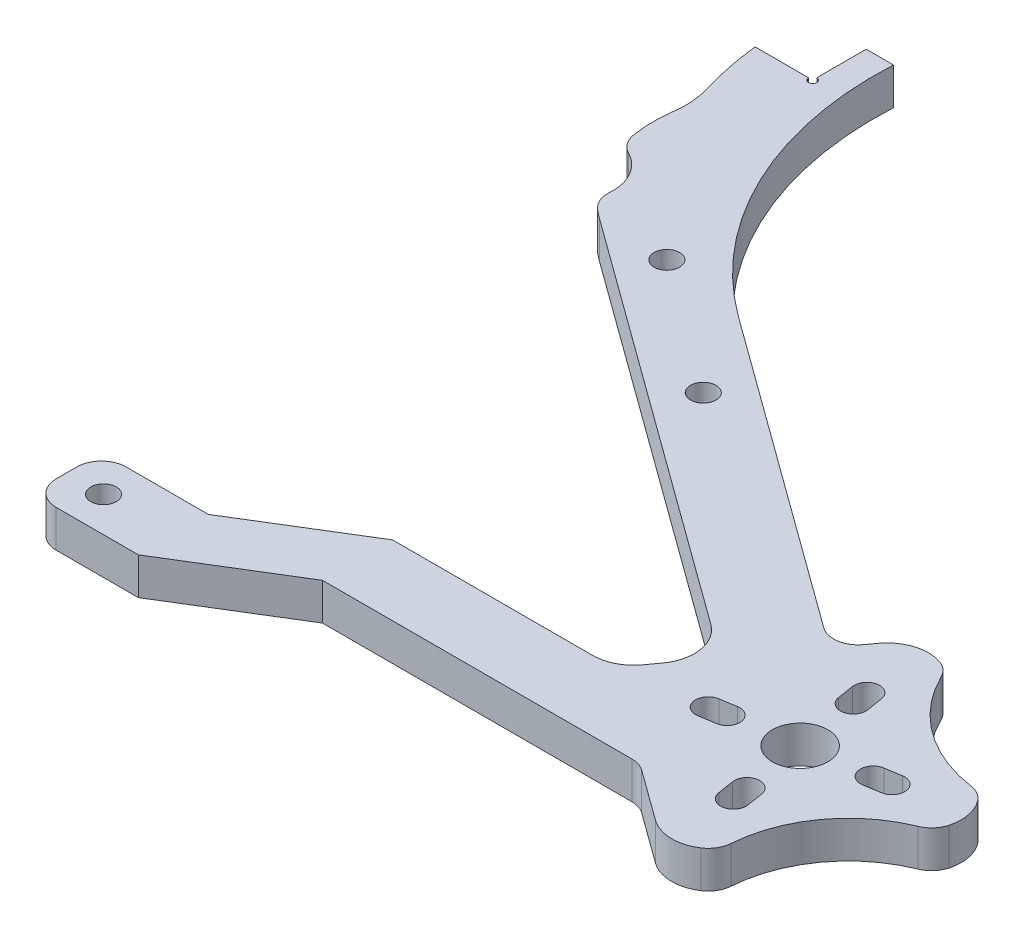
SolidWorks part; units mm, degrees
material "PPS"
ref_plane "前视基准面" through (0, 0, 0) normal (0, 0, 1) x (1, 0, 0)
ref_plane "上视基准面" through (0, 0, 0) normal (0, 1, 0) x (1, 0, 0)
ref_plane "右视基准面" through (0, 0, 0) normal (1, 0, 0) x (0, 0, -1)
sketch "草图3" plane through (0, 0, 0) normal (0, 1, 0) x (1, 0, 0)
  line L0 (0, 0) -> (35.4735, 0) construction
  line L1 (0, 0) -> (62.3757, -45.3186) construction
  line L2 (41.1319, -24.0128) -> (94.6944, -62.9282)
  line L3 (94.6944, -62.9282) -> (100.1314, -55.4448)
  line L4 (100.1314, -55.4448) -> (122.7839, -71.9028)
  line L5 (122.7839, -71.9028) -> (106.3259, -94.5552)
  line L6 (83.6734, -78.0972) -> (106.3259, -94.5552) construction
  line L9 (77.9994, -109.7251) -> (128.6275, -40.0415) construction
  line L11 (103.2286, -75) -> (90.242, -77.0569) construction
  line L13 (110.8832, -73.7876) -> (112.8586, -73.4748) construction
  line L14 (110.6408, -72.2567) -> (112.6161, -71.9438)
  line L15 (111.1257, -75.3185) -> (113.1011, -75.0057)
  line L16 (102.0163, -67.3454) -> (101.7034, -65.37) construction
  line L17 (103.5472, -67.1029) -> (103.2343, -65.1276)
  line L18 (100.4854, -67.5879) -> (100.1725, -65.6125)
  line L19 (95.5741, -76.2124) -> (93.5987, -76.5252) construction
  line L20 (95.8165, -77.7433) -> (93.8412, -78.0562)
  line L21 (95.3316, -74.6815) -> (93.3562, -74.9943)
  line L22 (104.441, -82.6546) -> (104.7539, -84.63) construction
  line L23 (102.9101, -82.8971) -> (103.223, -84.8724)
  line L24 (105.9719, -82.4121) -> (106.2848, -84.3875)
  line L36 (68.8077, -72) -> (90.242, -72) construction
  line L49 (89.1104, -70.6138) -> (83.6734, -78.0972)
  line L50 (35.5479, -31.6984) -> (89.1104, -70.6138)
  line L51 (83.6734, -78.0972) -> (30, -78.0972) construction
  line L52 (30, -78.0972) -> (30, -86.5972) construction
  line L53 (30, -86.5972) -> (95.3727, -86.5972) construction
  line L54 (95.3727, -86.5972) -> (106.3259, -94.5552)
  line L55 (83.6734, -78.0972) -> (56.8367, -78.0972)
  line L56 (95.3727, -86.5972) -> (56.8367, -86.5972)
  line L57 (56.8367, -78.0972) -> (42.9738, -86.5972)
  line L58 (42.9738, -86.5972) -> (30, -86.5972)
  line L59 (56.8367, -86.5972) -> (42.9738, -95.0972)
  line L60 (30, -86.5972) -> (30, -95.0972)
  line L61 (30, -95.0972) -> (42.9738, -95.0972)
  circle A5 centre (103.2286, -75) radius 3.375
  arc A6 (110.6408, -72.2567) -> (111.1257, -75.3185) centre (110.8832, -73.7876) ccw
  arc A7 (113.1011, -75.0057) -> (112.6161, -71.9438) centre (112.8586, -73.4748) ccw
  arc A8 (103.5472, -67.1029) -> (100.4854, -67.5879) centre (102.0163, -67.3454) cw
  arc A9 (100.1725, -65.6125) -> (103.2343, -65.1276) centre (101.7034, -65.37) cw
  arc A10 (95.8165, -77.7433) -> (95.3316, -74.6815) centre (95.5741, -76.2124) ccw
  arc A11 (93.3562, -74.9943) -> (93.8412, -78.0562) centre (93.5987, -76.5252) ccw
  arc A12 (102.9101, -82.8971) -> (105.9719, -82.4121) centre (104.441, -82.6546) cw
  arc A13 (106.2848, -84.3875) -> (103.223, -84.8724) centre (104.7539, -84.63) cw
  arc A16 (41.1319, -24.0128) -> (35.5479, -31.6984) centre (38.3399, -27.8556) ccw
  circle A17 centre (103.2286, -75) radius 66.25 construction
  circle A18 centre (44.0442, -32) radius 1.55
  circle A19 centre (60.2246, -43.7557) radius 1.55
  circle A20 centre (34.5, -90.8472) radius 1.55
  point P11 (114.5549, -83.229)
  point P20 (111.8709, -73.6312)
  point P27 (101.8598, -66.3577)
  point P35 (94.5864, -76.3688)
  point P42 (104.5974, -83.6423)
  point P54 (94.9997, -86.3262)
  point P69 (30, -90.8472)
  dimension "D2" = 45
  dimension "D3" = 6.75
  dimension "D4" = 1.55
  dimension "D7" = 14
  dimension "D11" = 132.5
  dimension "D12" = 3.1
  dimension "D16" = 3.1
  dimension "D1" = 36
  dimension "D5" = 2
  dimension "D6" = 7.75
  dimension "D8" = 14
  dimension "D9" = 4.75
  dimension "D10" = 75
  dimension "D13" = 32
  dimension "D14" = 20
  dimension "D15" = 8.5
  dimension "D17" = 34.5
  dimension "D18" = 4.5
  dimension "D19" = 90.8472
  dimension "D22" = 72
extrude "凸台-拉伸1" add sketch "草图3" along normal blind 4.5
fillet "圆角-美观1" radius 5 5 edges at (100.1314, 2.25, 55.4448) (122.7839, 2.25, 71.9028) (89.1104, 2.25, 70.6138) (106.3259, 2.25, 94.5552) (83.6734, 2.25, 78.0972)
sketch "草图4" plane through (0, 4.5, 0) normal (0, 1, 0) x (1, 0, 0)
  line L0 (104.1765, -58.3837) -> (118.7388, -68.9638)
  line L1 (119.8449, -75.9478) -> (109.2648, -90.5101)
  line L3 (103.2286, -75) -> (124.6569, -90.5685) construction
  line L4 (103.2286, -75) -> (89.033, -94.5387) construction
  line L5 (87.7185, -81.0362) -> (102.2808, -91.6163)
  arc A2 (102.2808, -91.6163) -> (87.7185, -81.0362) centre (86.1651, -98.4859) ccw
  arc A8 (118.7388, -68.9638) -> (104.1765, -58.3837) centre (120.2922, -51.5141) cw
  arc A9 (119.8449, -75.9478) -> (109.2648, -90.5101) centre (124.6569, -90.5685) ccw
  line M2 (118.7388, -68.9638) -> (104.1765, -58.3837)
  line M12 (109.2648, -90.5101) -> (119.8449, -75.9478)
extrude "圆弧-美观2" cut sketch "草图4" against normal up to next contours A8 M2 | A9 M12 region at (110.8688, 4.5, 64.4842) region at (113.6066, 4.5, 82.54)
fillet "圆角-美观3" radius 3 8 edges at (104.1765, 2.25, 58.3837) (118.7388, 2.25, 68.9638) (119.8449, 2.25, 75.9478) (94.6944, 2.25, 62.9282) (109.2648, 2.25, 90.5101) (30, 2.25, 95.0972) (95.3727, 2.25, 86.5972) (30, 2.25, 86.5972)
sketch "草图5" plane through (0, 0, 0) normal (0, 1, 0) x (1, 0, 0)
  line L0 (0, 0) -> (158.8801, 0) construction
  line L1 (0, 0) -> (0, -78.2587) construction
  line L2 (29.255, -13.8932) -> (40.1931, -23.471) construction
  line L3 (27.0025, -4.25) -> (34, -4.25)
  line L4 (34, -4.25) -> (34, 2.25)
  line L5 (34, -3.25) -> (26.9026, -3.25) construction
  line L6 (34, 3.25) -> (34, -3.25) construction
  line L7 (37.3772, 3.25) -> (34, 3.25) construction
  line L8 (41.1319, -24.0128) -> (54.395, -33.649)
  line L9 (34, 2.25) -> (37.3109, 2.25)
  line L10 (35.5479, -31.6984) -> (85.0653, -67.6749) construction
  line L11 (41.1319, -24.0128) -> (35.5479, -31.6984)
  arc A0 (26.9026, -3.25) -> (28.5167, -11.6611) centre (68.8233, 0.4342) ccw construction
  arc A5 (41.1319, -24.0128) -> (40.1931, -23.471) centre (38.2952, -27.8445) ccw
  arc A7 (40.1931, -23.471) -> (35.5479, -31.6984) centre (38.3022, -27.8285) ccw construction
  arc A8 (35.5479, -31.6984) -> (28.8424, -15.919) centre (45.3379, -18.2237) cw
  arc A9 (28.8424, -15.919) -> (28.5167, -11.6611) centre (18.9386, -14.5353) ccw
  arc A11 (37.3772, 3.25) -> (54.395, -33.649) centre (78.8424, 0) ccw
  arc A12 (27.0025, -4.25) -> (28.5167, -11.6611) centre (68.8233, 0.4342) ccw
  arc A13 (29.8202, 19.4008) -> (29.8202, -19.4008) centre (91.9966, 0) ccw construction
  arc A14 (54.395, 33.649) -> (54.395, -33.649) centre (78.8424, 0) ccw construction
  arc A15 (29.9602, 19.3706) -> (29.9602, -19.3706) centre (67.3193, 0) ccw construction
  dimension "D1" = 3.25
  dimension "D2" = 3.25
  dimension "D3" = 34
  dimension "D4" = 1
  dimension "D5" = 1
extrude "机臂配合防旋转" add sketch "草图5" along normal up to surface (4.5 mm away) contours L7 A0 A9 A8 A7 A5 L8 region at (35.1434, 0, 16.2105) up to face at (60.2246, 4.5, 45.3057)
sketch "草图7" plane through (0, 0, 0) normal (0, 1, 0) x (1, 0, 0)
  circle A6 centre (28, -28) radius 3.15 construction
  circle A7 centre (28, -28) radius 5.5
  circle A8 centre (44.0442, -32) radius 1.55 construction
  dimension "D1" = 11
  dimension "D2" = 16.0442
  dimension "D3" = 4
extrude "减震球让位" cut sketch "草图7" along normal through all
fillet "圆角1" radius 3 2 edges at (33.2399, 2.25, 29.6714) (29.2815, 2.25, 22.6514)
sketch "草图8" plane through (0, 4.5, 0) normal (0, 1, 0) x (1, 0, 0)
  circle A0 centre (34, -4.25) radius 0.5
  dimension "D1" = 1
extrude "直角约束" cut sketch "草图8" against normal through all
